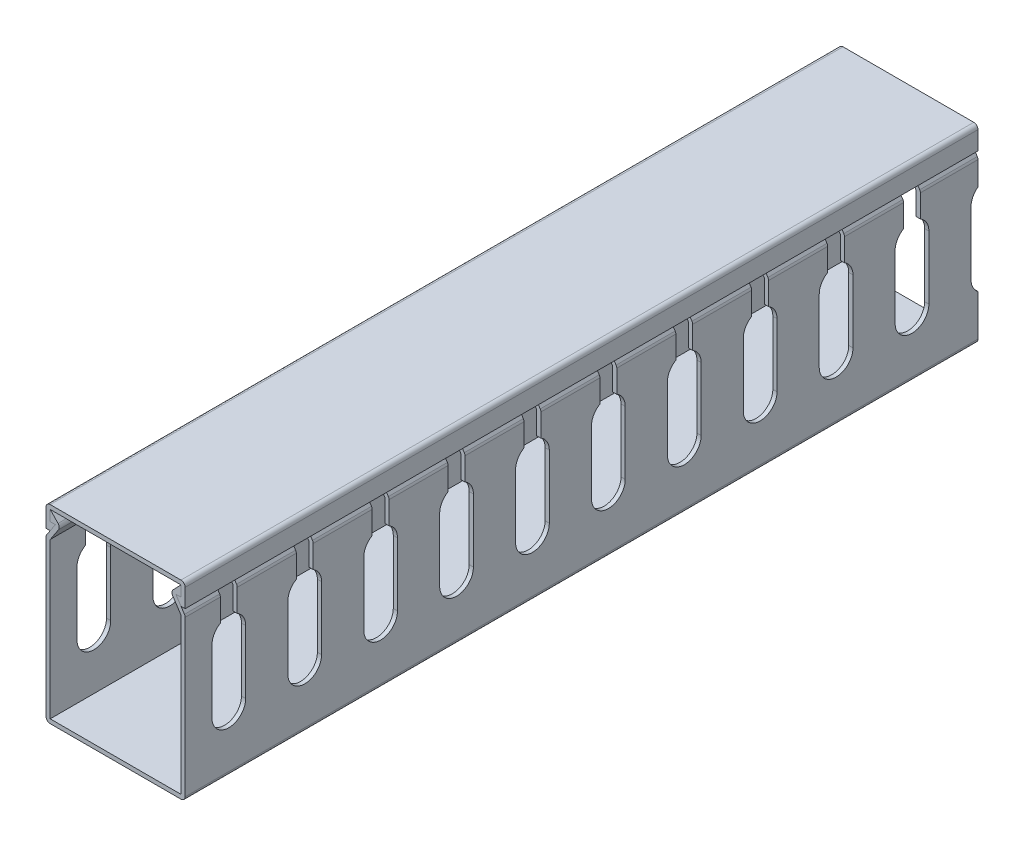
SolidWorks part; units mm, degrees
ref_plane "Front Plane" through (0, 0, 0) normal (0, 0, 1) x (1, 0, 0)
ref_plane "Top Plane" through (0, 0, 0) normal (0, 1, 0) x (1, 0, 0)
ref_plane "Right Plane" through (0, 0, 0) normal (1, 0, 0) x (0, 0, -1)
sketch "Sketch3" plane through (0, 0, 0) normal (0, 0, 1) x (1, 0, 0)
  line L234 (16.5, 37.8346) -> (16.5, 1)
  line L235 (16.3339, 38.3865) -> (14.281, 41.4887)
  line L236 (14.281, 41.4887) -> (15.5, 41.4887)
  line L237 (16.5, 39.6228) -> (16.5, 44)
  line L238 (16.5, 39.6228) -> (15.5158, 39.6228)
  line L239 (15.5, 41.4887) -> (15.5, 44)
  line L240 (15.5, 37.8346) -> (15.5, 1)
  line L241 (15.5, 37.8346) -> (13.5241, 40.8204)
  line L242 (13.6377, 42.0659) -> (15.5, 44)
  line L243 (-16.5, 37.8346) -> (-16.5, 1)
  line L244 (-16.3339, 38.3865) -> (-14.281, 41.4887)
  line L245 (-14.281, 41.4887) -> (-15.5, 41.4887)
  line L246 (-16.5, 39.6228) -> (-16.5, 44)
  line L247 (-16.5, 39.6228) -> (-15.5158, 39.6228)
  line L248 (-15.5, 41.4887) -> (-15.5, 44)
  line L249 (-15.5, 37.8346) -> (-15.5, 1)
  line L250 (-15.5, 37.8346) -> (-13.5241, 40.8204)
  line L251 (-13.6377, 42.0659) -> (-15.5, 44)
  line L252 (15.5, 0) -> (-15.5, 0)
  line L253 (15.5, 45) -> (-15.5, 45)
  line L254 (15.5, 1) -> (-15.5, 1)
  line L255 (15.5, 44) -> (-15.5, 44)
  arc A96 (16.5, 37.8346) -> (16.3339, 38.3865) centre (15.5, 37.8346) ccw
  arc A97 (13.6377, 42.0659) -> (13.5241, 40.8204) centre (14.358, 41.3723) ccw
  arc A98 (16.5, 44) -> (15.5, 45) centre (15.5, 44) ccw
  arc A99 (15.5, 0) -> (16.5, 1) centre (15.5, 1) ccw
  arc A100 (-16.3339, 38.3865) -> (-16.5, 37.8346) centre (-15.5, 37.8346) ccw
  arc A101 (-13.5241, 40.8204) -> (-13.6377, 42.0659) centre (-14.358, 41.3723) ccw
  arc A102 (-15.5, 45) -> (-16.5, 44) centre (-15.5, 44) ccw
  arc A103 (-16.5, 1) -> (-15.5, 0) centre (-15.5, 1) ccw
sketch "Sketch4" plane through (0, 0, 0) normal (0, 0, 1) x (1, 0, 0)
  line L0 (-15.5, 37.8346) -> (-15.5, 1)
  line L1 (-15.5, 1) -> (15.5, 1)
  line L2 (15.5, 1) -> (15.5, 37.8346)
  line L3 (15.5, 37.8346) -> (15.5, 1) construction
  line L4 (15.5, 37.8346) -> (13.5241, 40.8204)
  line L5 (13.6377, 42.0659) -> (15.5, 44)
  line L6 (15.5, 44) -> (15.5, 41.4887)
  line L7 (15.5, 41.4887) -> (14.281, 41.4887)
  line L8 (14.281, 41.4887) -> (16.3339, 38.3865)
  line L9 (16.5, 37.8346) -> (16.5, 1)
  line L10 (15.5, 0) -> (-15.5, 0)
  line L11 (-16.5, 1) -> (-16.5, 37.8346)
  line L12 (-16.3339, 38.3865) -> (-14.281, 41.4887)
  line L13 (-14.281, 41.4887) -> (-15.5, 41.4887)
  line L14 (-15.5, 41.4887) -> (-15.5, 44)
  line L15 (-15.5, 44) -> (-13.6377, 42.0659)
  line L16 (-13.5241, 40.8204) -> (-15.5, 37.8346)
  line L17 (-15.5, 37.8346) -> (-15.5055, 37.8438)
  arc A0 (13.5241, 40.8204) -> (13.6377, 42.0659) centre (14.358, 41.3723) cw
  arc A1 (16.3339, 38.3865) -> (16.5, 37.8346) centre (15.5, 37.8346) cw
  arc A2 (16.5, 1) -> (15.5, 0) centre (15.5, 1) cw
  arc A3 (-15.5, 0) -> (-16.5, 1) centre (-15.5, 1) cw
  arc A4 (-16.5, 37.8346) -> (-16.3339, 38.3865) centre (-15.5, 37.8346) cw
  arc A5 (-13.6377, 42.0659) -> (-13.5241, 40.8204) centre (-14.358, 41.3723) cw
extrude "Boss-Extrude1" add sketch "Sketch4" along normal mid plane 1700 contours A5 L15 L14 L13 L12 A4 L11 A3 L10 A2 L9 A1 L8 L7 L6 L5 A0 L4 L2 L1 L0 L16 region at (-16.05, 19.4173, 0)
sketch "Sketch5" plane through (0, 0, 0) normal (0, 0, 1) x (1, 0, 0)
  line L0 (-14.281, 41.4887) -> (-15.5158, 39.6228)
  line L1 (-15.5158, 39.6228) -> (-16.5, 39.6228)
  line L2 (-16.5, 39.6228) -> (-16.5, 44)
  line L3 (-15.5, 45) -> (15.5, 45)
  line L4 (16.5, 44) -> (16.5, 39.6228)
  line L5 (16.5, 39.6228) -> (15.5158, 39.6228)
  line L6 (15.5158, 39.6228) -> (14.281, 41.4887)
  line L7 (14.281, 41.4887) -> (15.5, 41.4887)
  line L8 (15.5, 41.4887) -> (15.5, 44)
  line L9 (15.5, 44) -> (-15.5, 44)
  line L10 (-15.5, 44) -> (-15.5, 41.4887)
  line L11 (-15.5, 41.4887) -> (-14.281, 41.4887)
  arc A0 (-16.5, 44) -> (-15.5, 45) centre (-15.5, 44) cw
  arc A1 (15.5, 45) -> (16.5, 44) centre (15.5, 44) cw
extrude "Boss-Extrude2" add sketch "Sketch5" along normal mid plane 1700 separate body
sketch "Sketch6" plane through (16.5, 0, 0) normal (1, 0, 0) x (0, 0, -1)
  line L0 (-839.65, 29) -> (-839.65, 14) construction
  line L1 (-835.65, 29) -> (-835.65, 14)
  line L2 (-843.65, 29) -> (-843.65, 14)
  line L3 (-850, 0) -> (850, 0) construction
  line L4 (-850, 37.8346) -> (-850, 1) construction
  line L6 (-841.65, 44) -> (-837.65, 44)
  line L7 (-841.65, 44) -> (-841.65, 32.4641)
  line L9 (-837.65, 44) -> (-837.65, 32.4641)
  line L10 (-850, 44) -> (850, 44) construction
  arc A0 (-835.65, 29) -> (-837.65, 32.4641) centre (-839.65, 29) ccw
  arc A1 (-843.65, 14) -> (-835.65, 14) centre (-839.65, 14) ccw
  arc A2 (-841.65, 32.4641) -> (-843.65, 29) centre (-839.65, 29) ccw
  dimension "D4" = 4
  dimension "D1" = 15
  dimension "D2" = 14
  dimension "D3" = 10.35
  dimension "D5" = 4
  dimension "D6" = 2
extrude "Cut-Extrude1" cut sketch "Sketch6" against normal through all
pattern_linear "LPattern1" count 94 spacing 18 along (0, 0, -1) of "Cut-Extrude1"
sketch "Sketch7" plane through (0, 45, 0) normal (0, 1, 0) x (1, 0, 0)
  line L1 (-23.8037, -850) -> (90.3306, -850)
  line L2 (-23.8037, -850) -> (-23.8037, -662)
  line L3 (-23.8037, -662) -> (90.3306, -662)
  line L4 (90.3306, -850) -> (90.3306, -662)
  line L5 (-42.6901, -918.4704) -> (818.6901, -918.4704)
  line L6 (-42.6901, -918.4704) -> (-42.6901, 1254.533)
  line L7 (-42.6901, 1254.533) -> (818.6901, 1254.533)
  line L8 (818.6901, -918.4704) -> (818.6901, 1254.533)
  dimension "D1" = 188
extrude "Cut-Extrude2" cut sketch "Sketch7" against normal blind 1339
